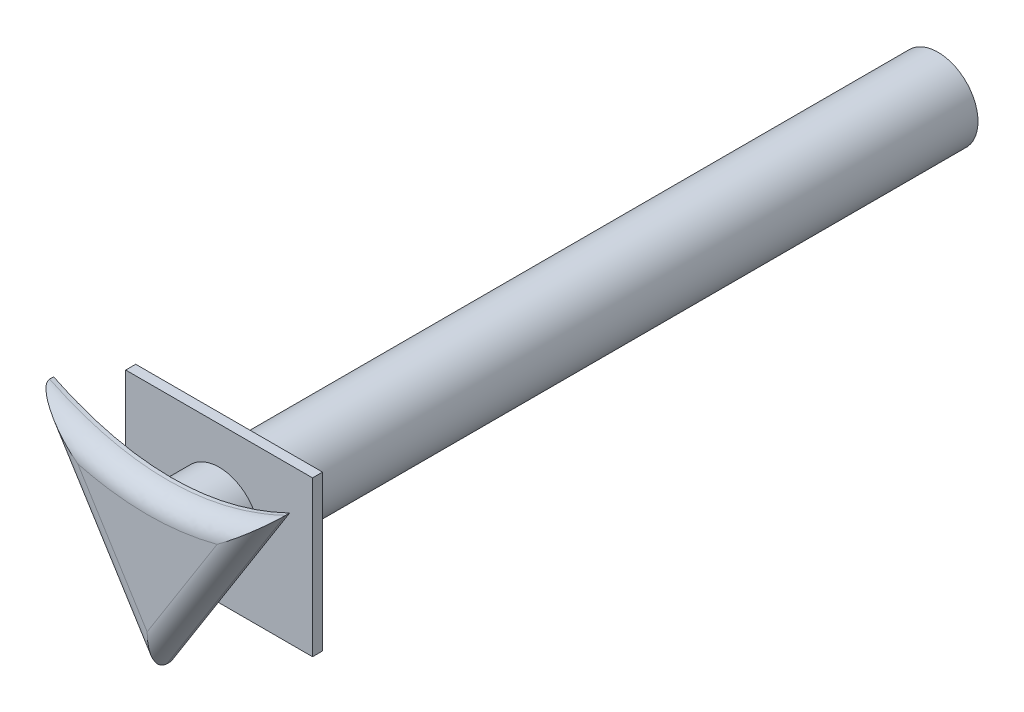
SolidWorks part; units mm, degrees
ref_plane "Front Plane" through (0, 0, 0) normal (0, 0, 1) x (1, 0, 0)
ref_plane "Top Plane" through (0, 0, 0) normal (0, 1, 0) x (1, 0, 0)
ref_plane "Right Plane" through (0, 0, 0) normal (1, 0, 0) x (0, 0, -1)
sketch "Sketch1" plane through (0, 0, 0) normal (0, 0, 1) x (1, 0, 0)
  circle A0 centre (36.163, 38.867) radius 2
  dimension "D1" = 4
extrude "Boss-Extrude1" add sketch "Sketch1" along normal blind 0.5 and the other way blind 38
sketch "Sketch2" plane through (0, 0, 0.5) normal (0, 0, 1) x (1, 0, 0)
  line L0 (36.163, 33.6651) -> (42.0844, 43.0432) construction
  line L1 (30.2979, 43.0432) -> (36.163, 33.6651) construction
  line L2 (36.163, 33.6651) -> (42.0844, 43.0432)
  line L3 (30.2979, 43.0432) -> (36.163, 33.6651)
  parabola Q0 (42.0844, 43.0432) -> (30.2979, 43.0432) focus (36.183, 47.721) apex (36.1763, 41.6201) construction
  parabola Q1 (42.0844, 43.0432) -> (30.2979, 43.0432) focus (36.183, 47.721) apex (36.1763, 41.6201)
extrude "Boss-Extrude2" add sketch "Sketch2" along normal blind 1 and the other way blind 0.2
fillet "Fillet1" radius 1 3 edges at (33.2305, 38.3542, 1.5) (39.1237, 38.3542, 1.5)
ref_plane "Plane1" through (0, 0, -2.1) normal (0, 0, 1) x (1, 0, 0)
sketch "Sketch3" plane through (0, 0, -2.1) normal (0, 0, 1) x (1, 0, 0)
  line L1 (31.4979, 42.7358) -> (40.8282, 42.7358)
  line L2 (31.4979, 42.7358) -> (31.4979, 34.9981)
  line L3 (31.4979, 34.9981) -> (40.8282, 34.9981)
  line L4 (40.8282, 42.7358) -> (40.8282, 34.9981)
  line L5 (31.4979, 42.7358) -> (40.8282, 34.9981) construction
  line L6 (31.4979, 34.9981) -> (40.8282, 42.7358) construction
  point P0 (36.163, 38.867)
extrude "Boss-Extrude3" add sketch "Sketch3" against normal blind 0.5
